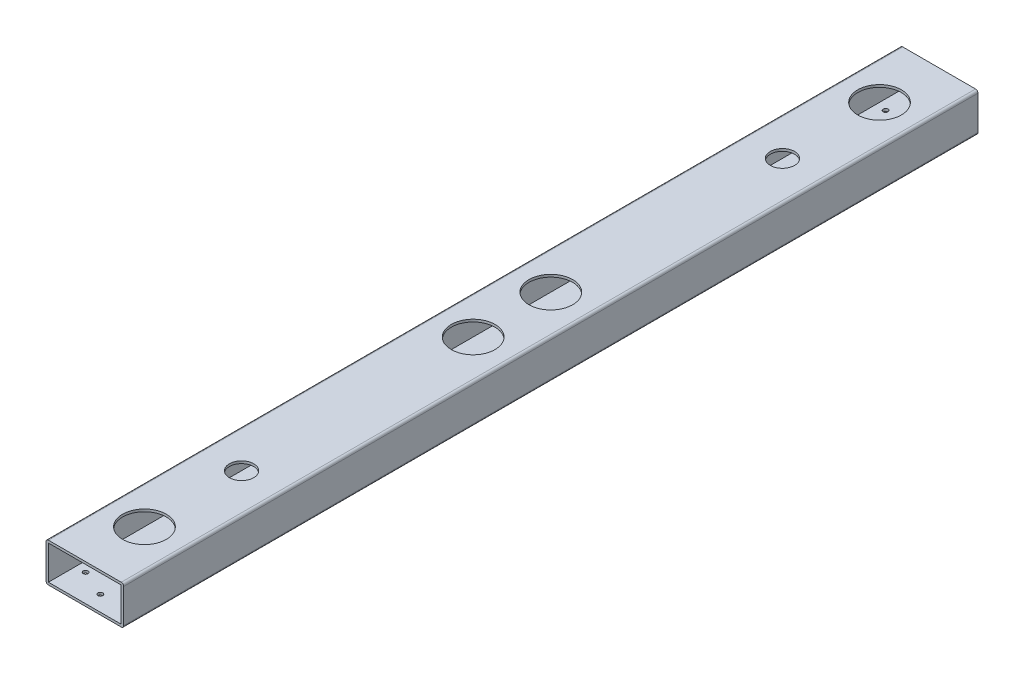
SolidWorks part; units mm, degrees
ref_plane "Front Plane" through (0, 0, 0) normal (0, 0, 1) x (1, 0, 0)
ref_plane "Top Plane" through (0, 0, 0) normal (0, 1, 0) x (1, 0, 0)
ref_plane "Right Plane" through (0, 0, 0) normal (1, 0, 0) x (0, 0, -1)
sketch "Sketch1" plane through (0, 0, 0) normal (0, 0, 1) x (1, 0, 0)
  line L0 (-23.8125, 11.1125) -> (23.8125, 11.1125)
  line L1 (-23.8125, -12.7) -> (23.8125, -12.7)
  line L2 (-25.4, -11.1125) -> (-25.4, 11.1125)
  line L3 (-23.8125, 12.7) -> (23.8125, 12.7)
  line L4 (25.4, -11.1125) -> (25.4, 11.1125)
  line L5 (-25.4, -12.7) -> (25.4, 12.7) construction
  line L6 (-25.4, 12.7) -> (25.4, -12.7) construction
  line L7 (23.8125, -11.1125) -> (23.8125, 11.1125)
  line L8 (-23.8125, -11.1125) -> (23.8125, -11.1125)
  line L9 (-23.8125, -11.1125) -> (-23.8125, 11.1125)
  line L10 (-25.4, -12.7) -> (25.4, -12.7) construction
  line L11 (-25.4, -12.7) -> (-25.4, 12.7) construction
  line L12 (25.4, -12.7) -> (25.4, 12.7) construction
  line L13 (-25.4, 12.7) -> (25.4, 12.7) construction
  arc A0 (-23.8125, -12.7) -> (-25.4, -11.1125) centre (-23.8125, -11.1125) cw
  arc A1 (23.8125, -12.7) -> (25.4, -11.1125) centre (23.8125, -11.1125) ccw
  arc A2 (23.8125, 12.7) -> (25.4, 11.1125) centre (23.8125, 11.1125) cw
  arc A3 (-25.4, 11.1125) -> (-23.8125, 12.7) centre (-23.8125, 11.1125) cw
  point P0 (0, 0)
  dimension "D4" = 1.5875
  dimension "D1" = 25.4
  dimension "D2" = 50.8
  dimension "D3" = 1.5875
extrude "Boss-Extrude1" add sketch "Sketch1" along normal blind 558.8
sketch "Sketch2" plane through (0, 12.7, 0) normal (0, 1, 0) x (1, 0, 0)
  line L2 (0, -519.8) -> (0, -304.8) construction
  line L3 (0, -304.8) -> (0, -254) construction
  line L4 (0, -254) -> (0, -39) construction
  line L5 (0, -519.8) -> (0, -558.8) construction
  line L6 (23.8125, -558.8) -> (-23.8125, -558.8) construction
  line L7 (0, -39) -> (0, 0) construction
  line L8 (23.8125, 0) -> (-23.8125, 0) construction
  circle A8 centre (0, -519.8) radius 14.2875
  circle A9 centre (0, -304.8) radius 14.2875
  circle A10 centre (0, -254) radius 14.2875
  circle A11 centre (0, -39) radius 14.2875
  point P7 (0, -212.7741)
  point P9 (0, -80.402)
  point P16 (0, -261.3622)
  dimension "D1" = 28.575
  dimension "D4" = 50.8
  dimension "D2" = 28.575
  dimension "D3" = 215
extrude "Cut-Extrude1" cut sketch "Sketch2" against normal up to next and the other way through all
sketch "Sketch3" plane through (0, -12.7, 0) normal (0, -1, 0) x (1, 0, 0)
  circle A0 centre (0, 39) radius 12.7
  circle A1 centre (0, 254) radius 12.7
  circle A2 centre (0, 304.8) radius 12.7
  circle A3 centre (0, 519.8) radius 12.7
  circle A4 centre (0, 519.8) radius 14.2875 construction
  circle A6 centre (0, 304.8) radius 14.2875 construction
  circle A7 centre (0, 254) radius 14.2875 construction
  circle A8 centre (0, 39) radius 14.2875 construction
  dimension "D1" = 25.4
  dimension "D2" = 25.4
extrude "Cut-Extrude2" cut sketch "Sketch3" against normal up to next and the other way through all
sketch "Sketch6" plane through (0, -12.7, 0) normal (0, -1, 0) x (1, 0, 0)
  line L0 (0, 39) -> (0, 254) construction
  line L1 (0, 304.8) -> (0, 519.8) construction
  circle A0 centre (0, 102.5) radius 3.3782
  circle A1 centre (0, 456.3) radius 3.3782
  dimension "D3" = 6.7564
  dimension "D1" = 63.5
  dimension "D2" = 63.5
extrude "Cut-Extrude5" cut sketch "Sketch6" against normal up to next and the other way through all
sketch "Sketch7" plane through (0, 12.7, 0) normal (0, 1, 0) x (1, 0, 0)
  line L0 (0, -39) -> (0, -254) construction
  line L1 (0, -304.8) -> (0, -519.8) construction
  circle A0 centre (0, -102.5) radius 7.9375
  circle A1 centre (0, -456.3) radius 7.9375
  circle A2 centre (0, -102.5) radius 3.3782 construction
  circle A3 centre (0, -456.3) radius 3.3782 construction
  dimension "D1" = 15.875
extrude "Cut-Extrude6" cut sketch "Sketch7" against normal up to next and the other way through all
sketch "Sketch8" plane through (0, -12.7, 0) normal (0, -1, 0) x (1, 0, 0)
  circle A0 centre (17.272, 541.02) radius 1.5875 construction
  circle A1 centre (0, 548.64) radius 1.5875 construction
  circle A2 centre (-17.272, 541.02) radius 1.5875 construction
  circle A3 centre (17.272, 541.02) radius 1.5875
  circle A4 centre (0, 548.64) radius 1.5875
  circle A5 centre (-17.272, 541.02) radius 1.5875
  circle A6 centre (-17.272, 17.78) radius 1.5875 construction
  circle A7 centre (0, 10.16) radius 1.5875 construction
  circle A8 centre (17.272, 17.78) radius 1.5875 construction
  circle A9 centre (-17.272, 17.78) radius 1.5875
  circle A10 centre (0, 10.16) radius 1.5875
  circle A11 centre (17.272, 17.78) radius 1.5875
extrude "Cut-Extrude7" cut sketch "Sketch8" against normal up to next and the other way through all
